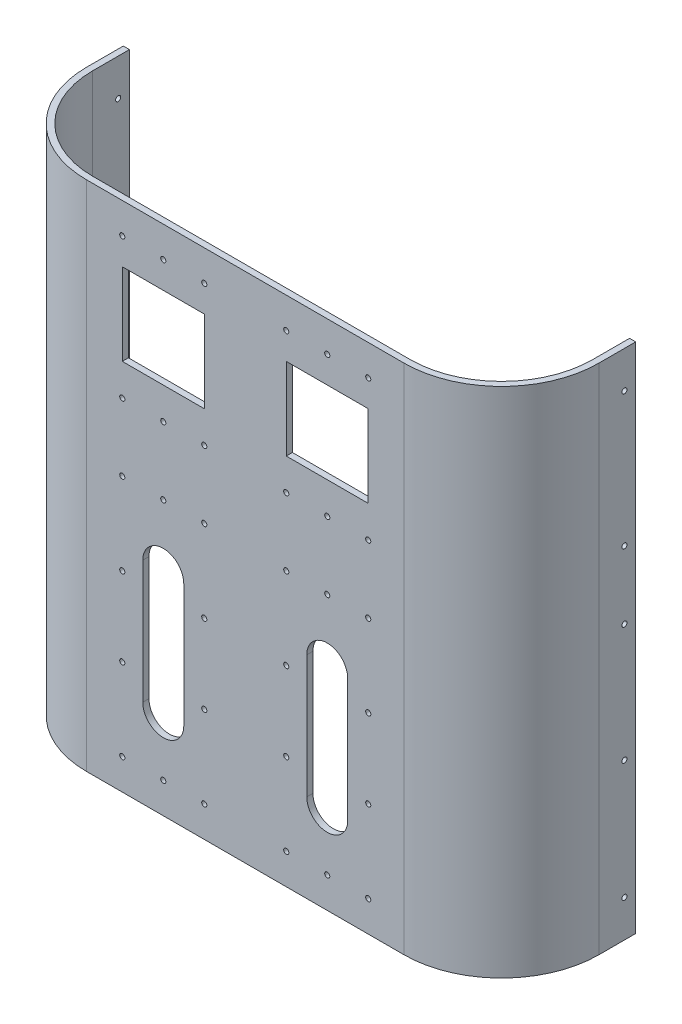
SolidWorks part; units mm, degrees
ref_plane "Спереди" through (0, 0, 0) normal (0, 0, 1) x (1, 0, 0)
ref_plane "Сверху" through (0, 0, 0) normal (0, 1, 0) x (1, 0, 0)
ref_plane "Справа" through (0, 0, 0) normal (1, 0, 0) x (0, 0, -1)
ref_plane "Плоскость4" through (0, 0, 56.5) normal (0, 0, 1) x (1, 0, 0)
sketch "Эскиз1" plane through (0, 0, 56.5) normal (0, 0, 1) x (1, 0, 0)
  line L0 (-125, 0) -> (125, 0)
  line L1 (125, 0) -> (125, 250)
  line L2 (125, 250) -> (-125, 250)
  line L3 (-125, 250) -> (-125, 0)
extrude "Бобышка-Вытянуть1" add sketch "Эскиз1" against normal blind 65.5
sketch "Эскиз2" plane through (0, 0, 0) normal (0, -1, 0) x (1, 0, 0)
  line L0 (122, -9) -> (122, 53.5)
  line L1 (122, 53.5) -> (-122, 53.5)
  line L2 (-122, 53.5) -> (-122, -9)
  line L3 (-122, -9) -> (122, -9)
extrude "Вырез-Вытянуть1" cut sketch "Эскиз2" against normal through all
sketch "Эскиз3" plane through (0, 0, 53.5) normal (0, 0, -1) x (-1, 0, 0)
  line L0 (20, 182) -> (60, 182)
  line L1 (60, 182) -> (60, 222)
  line L2 (60, 222) -> (20, 222)
  line L3 (20, 222) -> (20, 182)
extrude "Вырез-Вытянуть2" cut sketch "Эскиз3" against normal through all
sketch "Эскиз4" plane through (0, 0, 53.5) normal (0, 0, -1) x (-1, 0, 0)
  line L0 (-50, 103) -> (-50, 43)
  line L1 (-30, 43) -> (-30, 103)
  arc A0 (-50, 43) -> (-30, 43) centre (-40, 43) ccw
  arc A1 (-30, 103) -> (-50, 103) centre (-40, 103) ccw
extrude "Вырез-Вытянуть3" cut sketch "Эскиз4" against normal through all
sketch "Эскиз5" plane through (0, 0, 53.5) normal (0, 0, -1) x (-1, 0, 0)
  line L0 (-60, 182) -> (-20, 182)
  line L1 (-20, 182) -> (-20, 222)
  line L2 (-20, 222) -> (-60, 222)
  line L3 (-60, 222) -> (-60, 182)
extrude "Вырез-Вытянуть4" cut sketch "Эскиз5" against normal through all
sketch "Эскиз6" plane through (0, 0, 56.5) normal (0, 0, 1) x (1, 0, 0)
  line L0 (-30, 43) -> (-30, 103)
  line L1 (-50, 103) -> (-50, 43)
  arc A0 (-50, 43) -> (-30, 43) centre (-40, 43) ccw
  arc A1 (-30, 103) -> (-50, 103) centre (-40, 103) ccw
extrude "Вырез-Вытянуть5" cut sketch "Эскиз6" against normal through all
hole_wizard "Диаметр отверстия Ø2.5 (2.5)1" positions "Эскиз8" profile "Эскиз7" hole size "Ø2.5" standard "Ansi Metric"
sketch "Эскиз8" plane through (0, 0, 53.5) normal (0, 0, -1) x (-1, 0, 0)
  point P0 (60, 166.5)
  point P1 (20, 235)
  point P2 (20, 166.5)
  point P3 (-20, 133.5)
  point P4 (-20, 15)
  point P5 (-40, 166.5)
  point P6 (-40, 15)
  point P7 (-60, 235)
  point P8 (-60, 166.5)
  point P9 (60, 55)
  point P10 (20, 93.5)
  point P11 (20, 55)
  point P12 (-20, 93.5)
  point P13 (-20, 55)
  point P14 (-60, 93.5)
  point P15 (-60, 55)
  point P16 (60, 93.5)
  point P17 (-60, 15)
  point P18 (-60, 133.5)
  point P19 (-40, 133.5)
  point P20 (-40, 235)
  point P21 (-20, 166.5)
  point P22 (-20, 235)
  point P23 (20, 15)
  point P24 (20, 133.5)
  point P25 (40, 15)
  point P26 (40, 133.5)
  point P27 (40, 166.5)
  point P28 (40, 235)
  point P29 (60, 15)
  point P30 (60, 133.5)
  point P31 (60, 235)
sketch "Эскиз7" plane through (-60, 166.5, 53.5) normal (1, 0, 0) x (0, 1, 0)
  line L0 (0, 0) -> (0, 3)
  line L1 (0, 3) -> (1.25, 3)
  line L2 (1.25, 3) -> (1.25, 0)
  line L5 (1.25, 0) -> (0, 0)
  line L11 (0, -6.35) -> (0, 107.95) construction
  dimension "Диаметр сквозного отверстия" = 2.5
  dimension "Глубина сквозного отверстия" = 3
hole_wizard "Диаметр отверстия Ø2.5 (2.5)2" positions "Эскиз10" profile "Эскиз9" hole size "Ø2.5" standard "Ansi Metric"
sketch "Эскиз10" plane through (122, 0, 0) normal (-1, 0, 0) x (0, 0, 1)
  point P0 (-3.5, 232)
  point P1 (-3.5, 18)
  point P2 (-3.5, 76)
  point P3 (-3.5, 133.5)
  point P4 (-3.5, 166.5)
sketch "Эскиз9" plane through (122, 232, -3.5) normal (0, 1, 0) x (0, 0, 1)
  line L0 (0, 0) -> (0, 3)
  line L1 (0, 3) -> (1.25, 3)
  line L2 (1.25, 3) -> (1.25, 0)
  line L5 (1.25, 0) -> (0, 0)
  line L11 (0, -6.35) -> (0, 107.95) construction
  dimension "Диаметр сквозного отверстия" = 2.5
  dimension "Глубина сквозного отверстия" = 3
hole_wizard "Диаметр отверстия Ø2.5 (2.5)3" positions "Эскиз12" profile "Эскиз11" hole size "Ø2.5" standard "Ansi Metric"
sketch "Эскиз12" plane through (-122, 0, 0) normal (1, 0, 0) x (0, 0, -1)
  point P0 (3.5, 232)
  point P1 (3.5, 166.5)
  point P2 (3.5, 76)
  point P3 (3.5, 18)
  point P4 (3.5, 133.5)
sketch "Эскиз11" plane through (-122, 232, -3.5) normal (0, 1, 0) x (0, 0, -1)
  line L0 (0, 0) -> (0, 3)
  line L1 (0, 3) -> (1.25, 3)
  line L2 (1.25, 3) -> (1.25, 0)
  line L5 (1.25, 0) -> (0, 0)
  line L11 (0, -6.35) -> (0, 107.95) construction
  dimension "Диаметр сквозного отверстия" = 2.5
  dimension "Глубина сквозного отверстия" = 3
fillet "Скругление1" radius 44.5 2 edges at (-122, 125, 53.5) (122, 125, 53.5) tangent propagation no
fillet "Скругление2" radius 47.5 2 edges at (125, 125, 56.5) (-125, 125, 56.5) tangent propagation no
ref_axis "Ось1" through (0, 250, 53.5) along (0, -1, 0)
